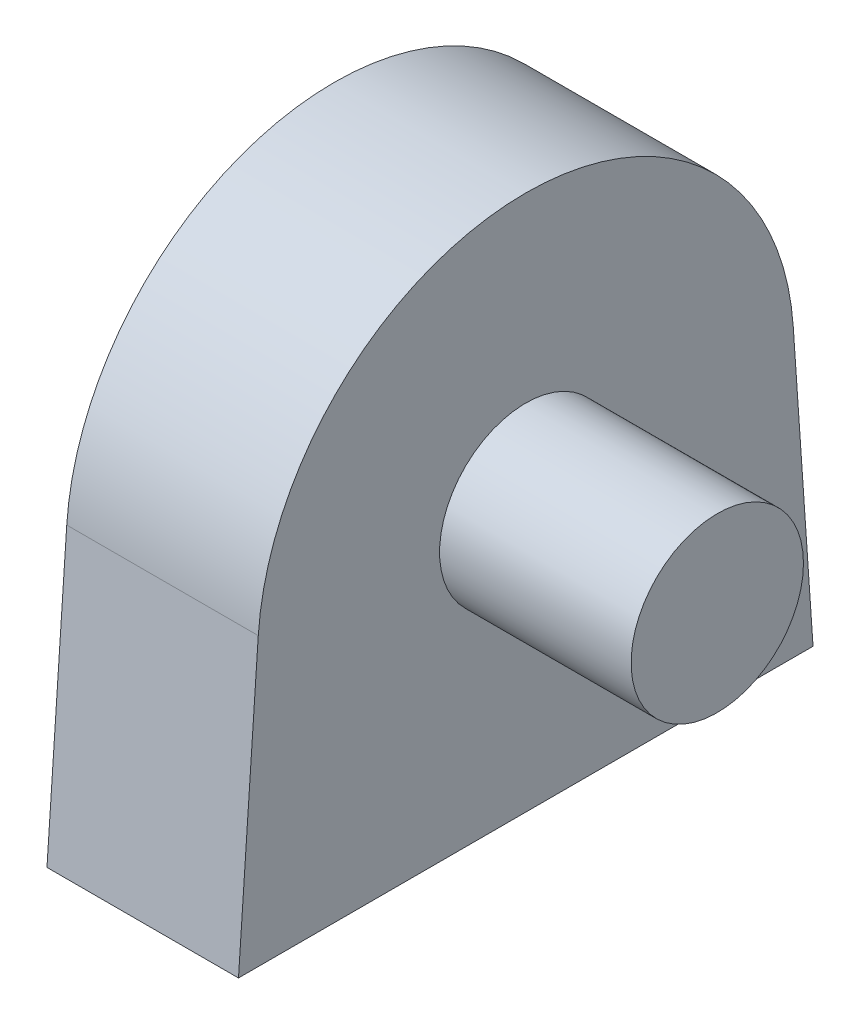
SolidWorks part; units mm, degrees
ref_plane "Front Plane" through (0, 0, 0) normal (0, 0, 1) x (1, 0, 0)
ref_plane "Top Plane" through (0, 0, 0) normal (0, 1, 0) x (1, 0, 0)
ref_plane "Right Plane" through (0, 0, 0) normal (1, 0, 0) x (0, 0, -1)
sketch "Sketch1" plane through (0, 0, 0) normal (1, 0, 0) x (0, 0, -1)
  line L0 (-15, 0) -> (15, 0)
  line L1 (-15, 0) -> (-9.5209, 17.0581)
  line L2 (9.5209, 17.0581) -> (15, 0)
  line L3 (0, 3) -> (-11, 3) construction
  line L4 (0, 25) -> (9.5209, 25) construction
  line L5 (0, 28) -> (15, 28) construction
  line L6 (-15, 0) -> (-13.5737, 20.6565) construction
  line L7 (0, 14) -> (0, 0) construction
  line L8 (15, 0) -> (13.5737, 20.6565) construction
  arc A0 (-9.5209, 17.0581) -> (9.5209, 17.0581) centre (0, 14) cw
  circle A1 centre (0, 14) radius 11 construction
  arc A2 (-12.5173, 7.7296) -> (13.1196, 9.1136) centre (0, 14) ccw construction
  arc A3 (13.9667, 14.9644) -> (-13.9667, 14.9644) centre (0, 14) ccw construction
  point P4 (0, 0)
  point P15 (7.5, 28)
  dimension "D2" = 10
  dimension "D4" = 22
  dimension "D1" = 30
  dimension "D3" = 14
  dimension "D5" = 3
extrude "Boss-Extrude1" add sketch "Sketch1" along normal blind 10
sketch "Sketch2" plane through (10, 0, 0) normal (1, 0, 0) x (0, 0, -1)
  circle A0 centre (0, 14) radius 4.5
  dimension "D1" = 9
extrude "Boss-Extrude2" add sketch "Sketch2" along normal blind 10
sketch "Sketch3" plane through (0, 0, 0) normal (0, -1, 0) x (1, 0, 0)
  line L0 (5, 7.5) -> (5, -7.5)
  line L1 (10, 15) -> (0, 15) construction
  circle A0 centre (5, 7.5) radius 1.5
  circle A1 centre (5, -7.5) radius 1.5
  point P7 (5, 15)
  point P8 (5, 0)
  dimension "D2" = 3
  dimension "D1" = 15
extrude "Cut-Extrude1" cut sketch "Sketch3" against normal blind 6 contours A0 | A1 region at (6.0307, 0, -6.4693) region at (3.9693, 0, 8.5307)
sketch "Sketch4" plane through (10, 0, 0) normal (1, 0, 0) x (0, 0, -1)
  line L0 (15, 0) -> (13.5737, 20.6565) construction
  line L1 (-15, 0) -> (-13.5737, 20.6565) construction
  line L2 (15, 0) -> (13.5737, 20.6565)
  line L3 (-15, 0) -> (15, 0)
  line L4 (15, 0) -> (9.5209, 17.0581)
  line L5 (-9.5209, 17.0581) -> (-15, 0)
  line L6 (-15, 0) -> (15, 0)
  line L7 (15, 0) -> (9.5209, 17.0581)
  line L8 (-9.5209, 17.0581) -> (-15, 0)
  line L9 (-15, 0) -> (-13.5737, 20.6565)
  arc A0 (13.9667, 14.9644) -> (-13.9667, 14.9644) centre (0, 14) ccw construction
  arc A1 (9.5209, 17.0581) -> (-9.5209, 17.0581) centre (0, 14) ccw
  arc A2 (9.5209, 17.0581) -> (-9.5209, 17.0581) centre (0, 14) ccw
  arc A3 (13.9667, 14.9644) -> (-13.9667, 14.9644) centre (0, 14) ccw
  arc M6 (9.5209, 17.0581) -> (-9.5209, 17.0581) centre (0, 14) ccw
  line M7 (-9.5209, 17.0581) -> (-15, 0)
  line M9 (15, 0) -> (9.5209, 17.0581)
  dimension "D1" = 0
extrude "Boss-Extrude3" add sketch "Sketch4" against normal up to surface (10 mm away) contours L2 A3 L9 M7 M6 M9 region at (10, 8.6546, -12.6512) up to face at (0, 10.2645, 0)
